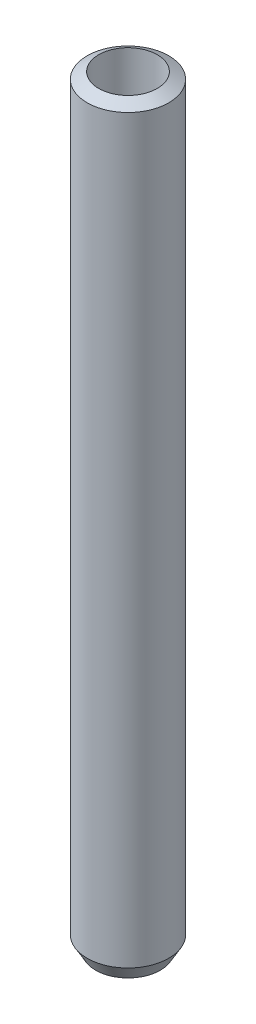
SolidWorks part; units mm, degrees
ref_plane "Front Plane" through (0, 0, 0) normal (0, 0, 1) x (1, 0, 0)
ref_plane "Top Plane" through (0, 0, 0) normal (0, 1, 0) x (1, 0, 0)
ref_plane "Right Plane" through (0, 0, 0) normal (1, 0, 0) x (0, 0, -1)
sketch "Sketch1" plane through (0, 0, 0) normal (0, 1, 0) x (1, 0, 0)
  circle A0 centre (0, 0) radius 12.5
  dimension "SHAFT_OD" = 25
extrude "Boss-Extrude1" add sketch "Sketch1" along normal blind 234.0954
sketch "Sketch2" plane through (0, 0, 0) normal (0, 1, 0) x (1, 0, 0)
  circle A0 centre (0, 0) radius 8.9727
  dimension "BORE_D" = 17.9453
extrude "Cut-Extrude1" cut sketch "Sketch2" along normal through all
chamfer "Chamfer1" distance 2.5836 angle 60 2 edges at (0, 234.0954, 12.5) (0, 0, 12.5) first distance on face at (0, 234.0954, 12.5) first distance on face at (0, 0, 8.9727)
